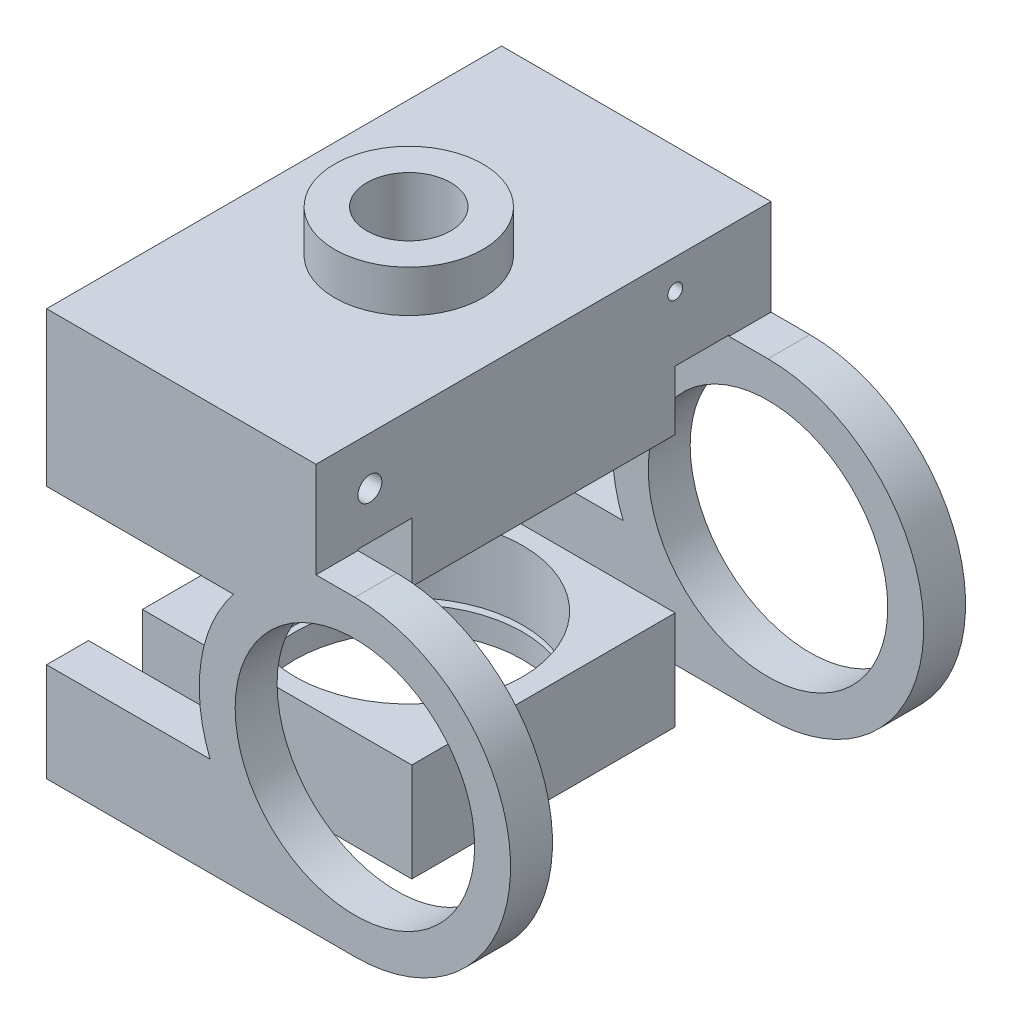
SolidWorks part; units mm, degrees
ref_plane "Plan de face" through (0, 0, 0) normal (0, 0, 1) x (1, 0, 0)
ref_plane "Plan de dessus" through (0, 0, 0) normal (0, 1, 0) x (1, 0, 0)
ref_plane "Plan de droite" through (0, 0, 0) normal (1, 0, 0) x (0, 0, -1)
sketch "Sketch4" plane through (0, 0, 0) normal (0, 0, 1) x (1, 0, 0)
  line L0 (0, 13) -> (-3.25, 13)
  line L1 (-3.25, 13) -> (-3.25, 21)
  line L2 (-3.25, 21) -> (-25.75, 21)
  line L3 (-25.75, 21) -> (-25.75, 8.15)
  line L4 (-25.75, 8.15) -> (-10.1281, 8.15)
  line L5 (0, -13) -> (-25.75, -13)
  line L6 (-25.75, -13) -> (-25.75, -4.75)
  line L7 (-25.75, -4.75) -> (-12.1011, -4.75)
  circle A0 centre (0, 0) radius 10
  arc A1 (-10.1281, 8.15) -> (-12.1011, -4.75) centre (0, 0) ccw
  arc A2 (0, -13) -> (0, 13) centre (0, 0) ccw
  dimension "D1" = 20
  dimension "D2" = 26
  dimension "D3" = 3.25
  dimension "D4" = 8
  dimension "D5" = 22.5
  dimension "D6" = 12.85
  dimension "D7" = 25.75
  dimension "D8" = 8.25
extrude "Boss-Extrude4" add sketch "Sketch4" along normal blind 3.5
sketch "Sketch5" plane through (0, 0, 3.5) normal (0, 0, 1) x (1, 0, 0)
  line L0 (-10.7623, 8.15) -> (-25.75, 8.15)
  line L1 (-25.75, 8.15) -> (-10.1281, 8.15) construction
  line L2 (-25.75, 8.15) -> (-25.75, 21)
  line L3 (-25.75, 21) -> (-3.25, 21)
  line L4 (-3.25, 21) -> (-3.25, 13.103)
  arc A0 (-3.25, 13.103) -> (-10.7623, 8.15) centre (0, 0) ccw
  dimension "D1" = 13.5
extrude "Boss-Extrude5" add sketch "Sketch5" along normal blind 4.5
sketch "Sketch6" plane through (0, 0, 8) normal (0, 0, 1) x (1, 0, 0)
  line L1 (-25.75, 21) -> (-3.25, 21)
  line L2 (-25.75, 21) -> (-25.75, 8.15)
  line L3 (-25.75, 8.15) -> (-3.25, 8.15)
  line L4 (-3.25, 21) -> (-3.25, 8.15)
  line L5 (-25.75, -13) -> (-3.25, -13)
  line L6 (-25.75, -13) -> (-25.75, -4.75)
  line L7 (-25.75, -4.75) -> (-3.25, -4.75)
  line L8 (-3.25, -13) -> (-3.25, -4.75)
  point P4 (0, 0)
  point P5 (0, 0)
  dimension "D1" = 22.5
  dimension "D2" = 12.9
extrude "Boss-Extrude6" add sketch "Sketch6" along normal blind 22
sketch "Sketch7" plane through (0, 0, 30) normal (0, 0, 1) x (1, 0, 0)
  line L1 (-25.75, 21) -> (-3.25, 21)
  line L2 (-25.75, 21) -> (-25.75, 8.15)
  line L3 (-25.75, 8.15) -> (-10.7623, 8.15)
  line L4 (-3.25, 21) -> (-3.25, 13.103)
  arc A0 (-3.25, 13.103) -> (-10.7623, 8.15) centre (0, 0) ccw
  point P4 (-3.25, -13)
  point P10 (0, 0)
  point P12 (0, 0)
  point P20 (-25.75, -4.75)
  dimension "D1" = 27
extrude "Boss-Extrude7" add sketch "Sketch7" along normal blind 4.5
sketch "Sketch8" plane through (0, 0, 34.5) normal (0, 0, 1) x (1, 0, 0)
  line L0 (0, 13) -> (-3.25, 13)
  line L3 (-3.25, 13) -> (-3.25, 21)
  line L4 (-3.25, 21) -> (-25.75, 21)
  line L5 (-25.75, 21) -> (-25.75, 8.15)
  line L6 (-25.75, 8.15) -> (-10.1281, 8.15)
  line L7 (-12.1011, -4.75) -> (-25.75, -4.75)
  line L8 (-25.75, -4.75) -> (-25.75, -13)
  line L9 (-25.75, -13) -> (0, -13)
  arc A0 (-10.1281, 8.15) -> (-12.1011, -4.75) centre (0, 0) ccw
  circle A1 centre (0, 0) radius 10
  arc A2 (0, -13) -> (0, 13) centre (0, 0) ccw
  dimension "D1" = 3.25
  dimension "D2" = 20
  dimension "D3" = 25.75
extrude "Boss-Extrude8" add sketch "Sketch8" along normal blind 3.5
sketch "Sketch9" plane through (0, 21, 0) normal (0, 1, 0) x (1, 0, 0)
  line L0 (-3.25, -38) -> (-25.75, -38) construction
  line L1 (-3.25, -38) -> (-3.25, 0) construction
  circle A0 centre (-14.5, -19) radius 6.187
  dimension "D1" = 19
  dimension "D2" = 11.25
extrude "Boss-Extrude9" add sketch "Sketch9" along normal blind 3.5
sketch "Sketch10" plane through (0, 24.5, 0) normal (0, 1, 0) x (1, 0, 0)
  circle A0 centre (-14.5, -19) radius 3.5
  dimension "D1" = 7
extrude "Cut-Extrude1" cut sketch "Sketch10" against normal blind 9.5 contours A0
sketch "Sketch11" plane through (0, 15, 0) normal (0, 1, 0) x (1, 0, 0)
  circle A0 centre (-14.5, -19) radius 8.5
  dimension "D1" = 17
extrude "Cut-Extrude2" cut sketch "Sketch11" against normal blind 0.5
sketch "Sketch12" plane through (0, 14.5, 0) normal (0, 1, 0) x (1, 0, 0)
  circle A0 centre (-14.5, -19) radius 9.5
  dimension "D1" = 19
extrude "Cut-Extrude3" cut sketch "Sketch12" against normal up to next (6.35 mm away)
sketch "Sketch13" plane through (0, -13, 0) normal (0, -1, 0) x (1, 0, 0)
  line L0 (-25.75, 30) -> (-25.75, 8) construction
  line L2 (-25.75, 8) -> (-3.25, 8) construction
  circle A0 centre (-14.5, 19) radius 9.5
  point P2 (0, 0)
  dimension "D1" = 11.25
  dimension "D3" = 19
  dimension "D2" = 11
extrude "Cut-Extrude4" cut sketch "Sketch13" against normal blind 2
sketch "Sketch14" plane through (0, -11, 0) normal (0, -1, 0) x (1, 0, 0)
  circle A0 centre (-14.5, 19) radius 10.5
  dimension "D1" = 21
extrude "Cut-Extrude5" cut sketch "Sketch14" against normal blind 0.5
sketch "Sketch15" plane through (0, -10.5, 0) normal (0, -1, 0) x (1, 0, 0)
  circle A0 centre (-14.5, 19) radius 9.5
  dimension "D1" = 19
extrude "Cut-Extrude6" cut sketch "Sketch15" against normal blind 5.75
sketch "Sketch18" plane through (-3.25, 0, 0) normal (1, 0, 0) x (0, 0, -1)
  line L0 (0, 13) -> (0, 21) construction
  line L1 (-38, 21) -> (0, 21) construction
  point P0 (-8, 18.5)
  dimension "D1" = 8
  dimension "D2" = 2.5
hole_wizard "Tap Drill for M1.6 Tap1" positions "Sketch18" profile "Sketch17" hole size "M1.6" standard "ISO"
sketch "Sketch17" plane through (-3.25, 18.5, 8) normal (0, 1, 0) x (0, 0, -1)
  line L0 (0, 0) -> (0, 5.8755)
  line L1 (0, 5.8755) -> (0.625, 5.5)
  line L2 (0.625, 5.5) -> (0.625, 0)
  line L5 (0.625, 0) -> (0, 0)
  line L10 (0, 5.8755) -> (-0.625, 5.5) construction
  line L11 (0, -6.35) -> (0, 107.95) construction
  dimension "Hole Dia." = 1.25
  dimension "Hole Depth" = 5.5
  dimension "Drill Angle" = 118
cosmetic thread "Cosmetic Thread1" parameters "D1"=4.5, "D2"=2.2
sketch "Sketch21" plane through (-3.25, 0, 0) normal (1, 0, 0) x (0, 0, -1)
  line L0 (-38, 13) -> (-38, 21) construction
  line L1 (-38, 21) -> (0, 21) construction
  point P0 (-33.5, 17)
  dimension "D1" = 4.5
  dimension "D2" = 4
hole_wizard "Ø2.0 (2) Diameter Hole1" positions "Sketch21" profile "Sketch20" hole size "Ø2.0" standard "ISO" end condition through all
sketch "Sketch20" plane through (-3.25, 17, 33.5) normal (0, 1, 0) x (0, 0, -1)
  line L0 (0, 0) -> (0, 22.5)
  line L1 (0, 22.5) -> (1, 22.5)
  line L2 (1, 22.5) -> (1, 0)
  line L5 (1, 0) -> (0, 0)
  line L11 (0, -6.35) -> (0, 107.95) construction
  dimension "Thru Hole Dia." = 2
  dimension "Thru Hole Depth" = 22.5
